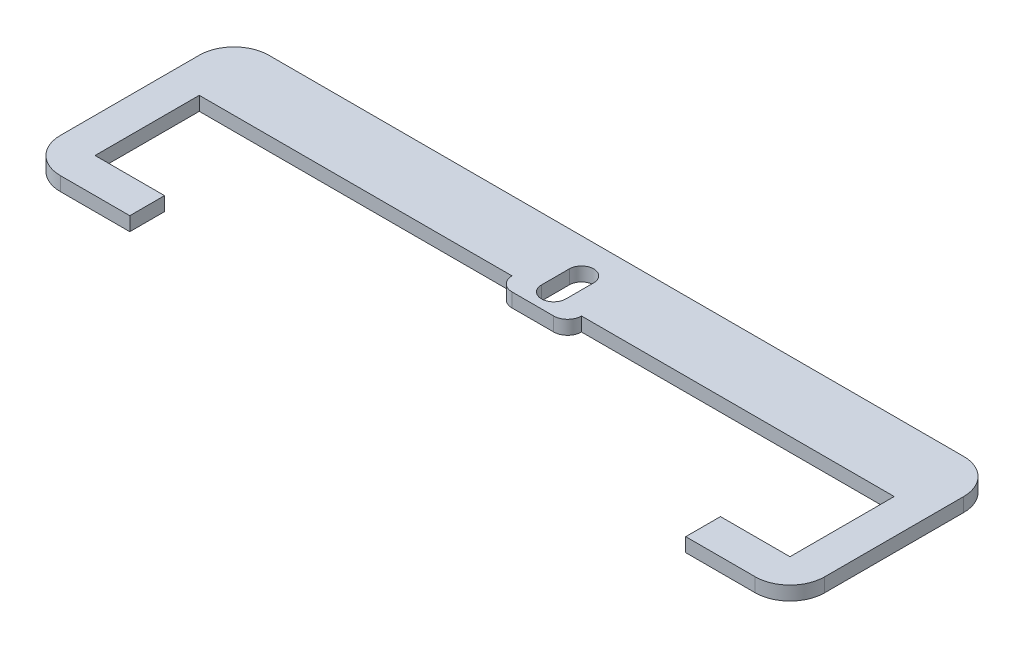
SolidWorks part; units mm, degrees
ref_plane "Front Plane" through (0, 0, 0) normal (0, 0, 1) x (1, 0, 0)
ref_plane "Top Plane" through (0, 0, 0) normal (0, 1, 0) x (1, 0, 0)
ref_plane "Right Plane" through (0, 0, 0) normal (1, 0, 0) x (0, 0, -1)
sketch "Sketch1" plane through (0, 0, 0) normal (0, 1, 0) x (1, 0, 0)
  line L1 (-139.7, -38.1) -> (139.7, -38.1)
  line L2 (-139.7, -38.1) -> (-139.7, 38.1)
  line L3 (-139.7, 38.1) -> (139.7, 38.1)
  line L4 (139.7, -38.1) -> (139.7, 38.1)
  line L5 (-139.7, -38.1) -> (139.7, 38.1) construction
  line L6 (-139.7, 38.1) -> (139.7, -38.1) construction
  point P0 (0, 0)
  dimension "D1" = 279.4
  dimension "D2" = 76.2
extrude "Boss-Extrude1" add sketch "Sketch1" along normal blind 5.08
sketch "Sketch2" plane through (0, 5.08, 0) normal (0, 1, 0) x (1, 0, 0)
  line L5 (0, -38.1) -> (0, -6.35) construction
  line L6 (-139.7, -38.1) -> (139.7, -38.1) construction
  line L9 (127, -25.4) -> (-127, -25.4)
  line L11 (127, -25.4) -> (127, 12.7)
  line L12 (127, 12.7) -> (-127, 12.7)
  line L13 (-127, -25.4) -> (-127, 12.7)
  line L14 (127, -25.4) -> (-127, 12.7) construction
  line L15 (127, 12.7) -> (-127, -25.4) construction
  dimension "D1" = 38.1
  dimension "D2" = 31.75
  dimension "D3" = 254
extrude "Cut-Extrude1" cut sketch "Sketch2" against normal through all
fillet "Fillet1" radius 12.7 2 edges at (-139.7, 2.54, -38.1) (139.7, 2.54, -38.1)
fillet "Fillet2" radius 12.7 2 edges at (-139.7, 2.54, 38.1) (139.7, 2.54, 38.1)
sketch "Sketch4" plane through (0, 5.08, 0) normal (0, 1, 0) x (1, 0, 0)
  line L0 (0, -25.4) -> (0, -38.1) construction
  line L1 (-127, -25.4) -> (127, -25.4) construction
  line L2 (-127, -38.1) -> (127, -38.1) construction
  line L4 (-101.6, -38.1) -> (101.6, -38.1)
  line L5 (-101.6, -38.1) -> (-101.6, -25.4)
  line L6 (-101.6, -25.4) -> (101.6, -25.4)
  line L7 (101.6, -38.1) -> (101.6, -25.4)
  line L8 (-101.6, -38.1) -> (101.6, -25.4) construction
  line L9 (-101.6, -25.4) -> (101.6, -38.1) construction
  point P6 (0, -31.75)
  dimension "D1" = 203.2
extrude "Cut-Extrude2" cut sketch "Sketch4" against normal through all
sketch "Sketch5" plane through (0, 0, -12.7) normal (0, 0, 1) x (1, 0, 0)
  line L0 (0, 0) -> (0, 5.08) construction
  line L1 (127, 0) -> (-127, 0) construction
  line L2 (127, 5.08) -> (-127, 5.08) construction
  line L4 (-12.7, 0) -> (12.7, 0)
  line L5 (-12.7, 0) -> (-12.7, 5.08)
  line L6 (-12.7, 5.08) -> (12.7, 5.08)
  line L7 (12.7, 0) -> (12.7, 5.08)
  line L8 (-12.7, 0) -> (12.7, 5.08) construction
  line L9 (-12.7, 5.08) -> (12.7, 0) construction
  point P6 (0, 2.54)
  dimension "D1" = 25.4
extrude "Boss-Extrude2" add sketch "Sketch5" along normal blind 5.08
fillet "Fillet3" radius 5.08 2 edges at (-12.7, 2.54, -7.62) (12.7, 2.54, -7.62)
sketch "Sketch6" plane through (0, 5.08, 0) normal (0, 1, 0) x (1, 0, 0)
  line L0 (0, 38.1) -> (0, 15.24) construction
  line L1 (127, 38.1) -> (-127, 38.1) construction
  line L2 (0, 15.24) -> (0, 25.4) construction
  line L3 (-4.445, 15.24) -> (-4.445, 25.4)
  line L4 (4.445, 15.24) -> (4.445, 25.4)
  arc A0 (-4.445, 15.24) -> (4.445, 15.24) centre (0, 15.24) ccw
  arc A1 (4.445, 25.4) -> (-4.445, 25.4) centre (0, 25.4) ccw
  point P5 (0, 20.32)
  dimension "D1" = 22.86
extrude "Cut-Extrude4" cut sketch "Sketch6" against normal through all
equation "\"Foamcore\" = .1in"
equation "\"MDF\" = .2in"
equation "\"Gmaterial\"= \"MDF\""
equation "\"PVC-ID\" = \"1.590in\""
equation "\"PVC-OD\" = \"1.900in\""
equation "\"D1@Boss-Extrude1\"=\"Gmaterial\""
